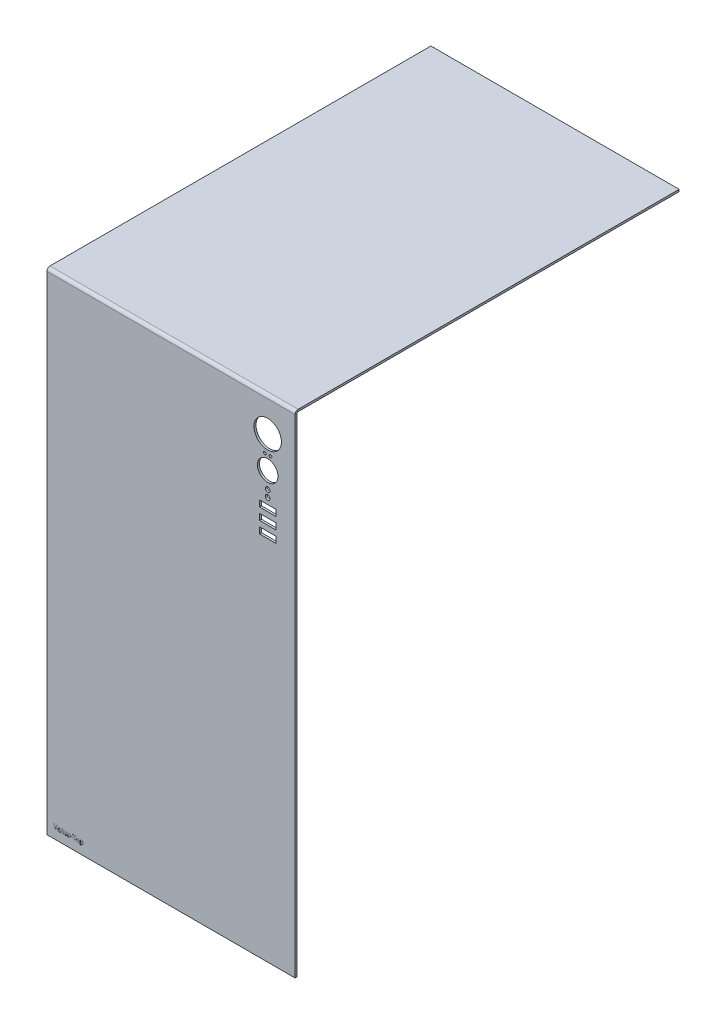
SolidWorks part; units mm, degrees
note: The reader was unsure of these and kept them because the rebuilt part matched: flange length of "Edge-Flange1".
material "6061-T6 (SS)"
ref_plane "Front Plane" through (0, 0, 0) normal (0, 0, 1) x (1, 0, 0)
ref_plane "Top Plane" through (0, 0, 0) normal (0, 1, 0) x (1, 0, 0)
ref_plane "Right Plane" through (0, 0, 0) normal (1, 0, 0) x (0, 0, -1)
sketch "Sketch1" plane through (0, 0, 0) normal (0, 0, 1) x (1, 0, 0)
  line L1 (0, 0) -> (181, 0)
  line L2 (0, 0) -> (0, -358)
  line L3 (0, -358) -> (181, -358)
  line L4 (181, 0) -> (181, -358)
  dimension "D1" = 181
  dimension "D2" = 358
base flange "Base-Flange1" sketch "Sketch1" thickness 1.5 reverse thickness direction no parameters "D1"=0.7366
edge flange "Edge-Flange1" sketch "Sketch8" flange angle 90 flange length 280 flange position material inside bend radius 0.7366 thickness 1.5 relief rectangular parameters "D6"=10
sketch "Sketch8" plane through (0, 0, -1.5) normal (0, 1, 0) x (1, 0, 0)
  line L2 (0, 0) -> (0, 278.5)
  line L3 (0, 278.5) -> (181, 278.5)
  line L4 (181, 278.5) -> (181, 0)
  line L11 (181, 0) -> (0, 0) construction
  line L12 (181, 0) -> (0, 0)
bend "EdgeBend1" bend radius 0.7366 bend angle 90 parameters "D5"=1
sketch "Sketch9" plane through (0, 0, 0) normal (0, 0, 1) x (1, 0, 0)
  line L0 (161, -2.2366) -> (161, -191.6907) construction
  line L1 (181, -2.2366) -> (0, -2.2366) construction
  line L3 (155, -73.5663) -> (167, -73.5663)
  line L4 (155, -73.5663) -> (155, -69.0663)
  line L5 (155, -69.0663) -> (167, -69.0663)
  line L6 (167, -73.5663) -> (167, -69.0663)
  line L7 (155, -73.5663) -> (167, -69.0663) construction
  line L8 (155, -69.0663) -> (167, -73.5663) construction
  line L9 (155, -77.5663) -> (167, -77.5663)
  line L10 (155, -77.5663) -> (155, -82.0663)
  line L11 (155, -82.0663) -> (167, -82.0663)
  line L12 (167, -77.5663) -> (167, -82.0663)
  line L13 (155, -77.5663) -> (167, -82.0663) construction
  line L14 (155, -82.0663) -> (167, -77.5663) construction
  line L15 (155, -90.5663) -> (167, -90.5663)
  line L16 (155, -90.5663) -> (155, -86.0663)
  line L17 (155, -86.0663) -> (167, -86.0663)
  line L18 (167, -90.5663) -> (167, -86.0663)
  line L19 (155, -90.5663) -> (167, -86.0663) construction
  line L20 (155, -86.0663) -> (167, -90.5663) construction
  circle A0 centre (161, -24.5663) radius 10
  circle A1 centre (161, -47.5663) radius 7.5
  circle A2 centre (159, -37.5663) radius 1
  circle A3 centre (163, -37.5663) radius 1
  circle A4 centre (161, -59.5663) radius 1.75
  circle A5 centre (161, -64.5663) radius 1.75
  point P16 (161, -88.3163)
  point P17 (161, -79.8163)
  point P20 (161, -71.3163)
  dimension "D1" = 2
  dimension "D3" = 12
  dimension "D8" = 4.5
  dimension "D10" = 5
  dimension "D11" = 13
  dimension "D2" = 2
  dimension "D4" = 4.5
  dimension "D5" = 12
  dimension "4.5" = 4.5
  dimension "D6" = 12
  dimension "D7" = 4.5
  dimension "D9" = 4
  dimension "4" = 4
  dimension "12" = 12
  dimension "10" = 10
  dimension "D12" = 20
extrude "Cut-Extrude1" cut sketch "Sketch9" against normal up to next normal cut yes
sketch "Sketch10" plane through (0, 0, 0) normal (0, 0, 1) x (1, 0, 0)
  line L0 (4.8823, -351.6341) -> (32.9758, -351.6341) construction
  text T0 "<b>Value-Top</b>" font "Franklin Gothic Book" height 3.5
extrude "Cut-Extrude2" cut sketch "Sketch10" against normal blind 0.05 normal cut yes
sketch "Bend-Lines1" [suppressed] plane through (0, 0, 0) normal (0, 1, 0) x (1, 0, 0)
sketch "Bounding-Box1" [suppressed] plane through (0, 0, 0) normal (0, 1, 0) x (1, 0, 0)
sheet metal parameters "Sheet-Metal1" thickness 1.5 parameters "D1"=0.7366
flat pattern "Flat-Pattern1" [suppressed]
sketch "Bend-Lines2" plane through (0, 0, 0) normal (0, 1, 0) x (1, 0, 0)
sketch3d "Bounding-Box2" [suppressed]
  line L0 (-181, 0, 0) -> (-181, -358, 0) construction
  line L1 (0, 0, 0) -> (0, -358, 0) construction
  line L2 (-181, 0, 0) -> (0, 0, 0) construction
  line L3 (-181, -358, 0) -> (0, -358, 0) construction
sheet metal parameters "Sheet-Metal2" thickness 1.5 parameters "D1"=0.7366
flat pattern "Flat-Pattern1"
sketch "Bend-Lines2" plane through (0, 0, 0) normal (0, 0, 1) x (1, 0, 0)
  line L0 (181, -1.069) -> (0, -1.069) construction
  line L1 (181, -1.069) -> (0, -1.069) construction
sketch3d "Bounding-Box2" [suppressed]
  line L0 (181, 277.8619, 0) -> (181, -358, 0) construction
  line L1 (0, 277.8619, 0) -> (0, -358, 0) construction
  line L2 (181, 277.8619, 0) -> (0, 277.8619, 0) construction
  line L3 (181, -358, 0) -> (0, -358, 0) construction
bend of the flat pattern "Flatten-<EdgeBend1>1"
sheet metal parameters "Sheet-Metal3" thickness 1.5 parameters "D1"=0.7366
flat pattern "Flat-Pattern1"
sketch "Bend-Lines2" plane through (0, 0, 0) normal (0, 0, 1) x (1, 0, 0)
  line L0 (181, -1.069) -> (0, -1.069) construction
  line L1 (181, -1.069) -> (0, -1.069) construction
sketch3d "Bounding-Box2" [suppressed]
  line L0 (181, 277.8619, 0) -> (181, -358, 0) construction
  line L1 (0, 277.8619, 0) -> (0, -358, 0) construction
  line L2 (181, 277.8619, 0) -> (0, 277.8619, 0) construction
  line L3 (181, -358, 0) -> (0, -358, 0) construction
bend of the flat pattern "Flatten-<EdgeBend1>1"
sheet metal parameters "Sheet-Metal4" thickness 1.5 parameters "D1"=0.7366
flat pattern "Flat-Pattern1"
sketch "Bend-Lines2" plane through (0, 0, 0) normal (0, 0, 1) x (1, 0, 0)
  line L0 (181, -1.069) -> (0, -1.069) construction
  line L1 (181, -1.069) -> (0, -1.069) construction
sketch3d "Bounding-Box2" [suppressed]
  line L0 (181, 277.8619, 0) -> (181, -358, 0) construction
  line L1 (0, 277.8619, 0) -> (0, -358, 0) construction
  line L2 (181, 277.8619, 0) -> (0, 277.8619, 0) construction
  line L3 (181, -358, 0) -> (0, -358, 0) construction
bend of the flat pattern "Flatten-<EdgeBend1>1"
